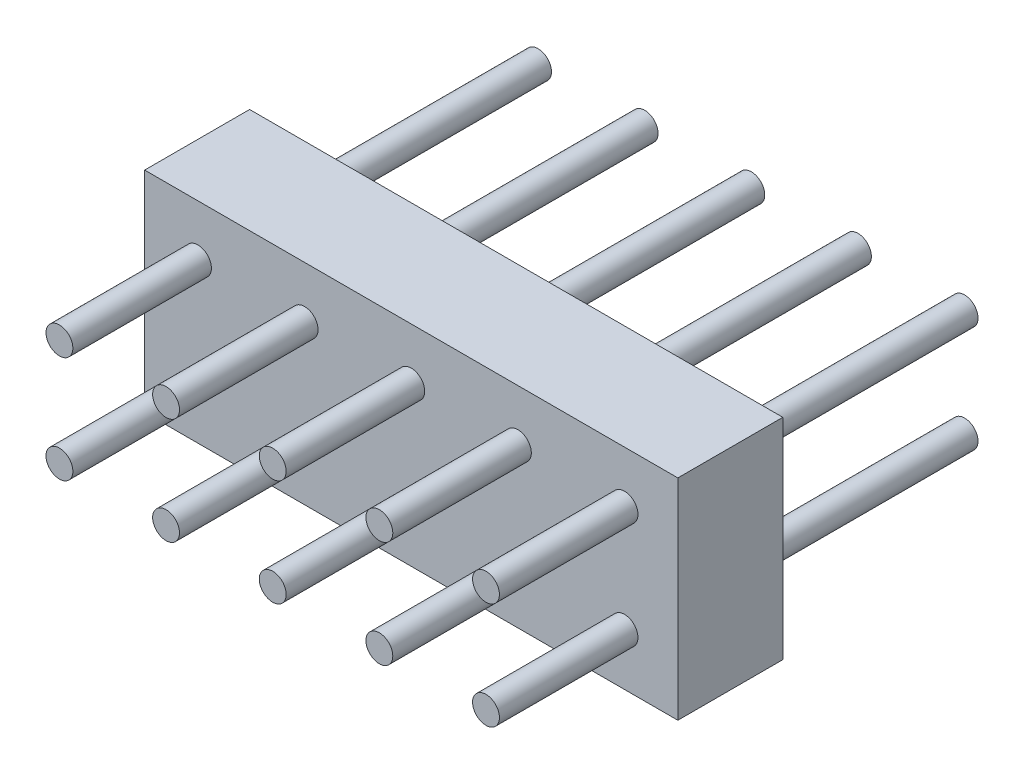
SolidWorks part; units mm, degrees
ref_plane "前视基准面" through (0, 0, 0) normal (0, 0, 1) x (1, 0, 0)
ref_plane "上视基准面" through (0, 0, 0) normal (0, 1, 0) x (1, 0, 0)
ref_plane "右视基准面" through (0, 0, 0) normal (1, 0, 0) x (0, 0, -1)
sketch "Sketch1" plane through (0, 0, 0) normal (0, 0, 1) x (1, 0, 0)
  line L1 (0, 0) -> (12.7, 0)
  line L2 (0, 0) -> (0, 5)
  line L3 (0, 5) -> (12.7, 5)
  line L4 (12.7, 0) -> (12.7, 5)
extrude "Boss-Extrude1" add sketch "Sketch1" along normal blind 2.5 contours L3 L4 L1 L2
sketch "Sketch2" plane through (0, 0, 2.5) normal (0, 0, 1) x (1, 0, 0)
  line L0 (0, 2.5) -> (14.858, 2.5) construction
  line L1 (0, 0) -> (0, 5) construction
  line L2 (6.35, 5) -> (6.35, -2.9072) construction
  line L3 (0, 5) -> (12.7, 5) construction
  circle A0 centre (1.27, 1.23) radius 0.32
  circle A1 centre (3.81, 1.23) radius 0.32
  circle A2 centre (6.35, 1.23) radius 0.32
  circle A3 centre (8.89, 1.23) radius 0.32
  circle A4 centre (11.43, 1.23) radius 0.32
  circle A5 centre (11.43, 3.77) radius 0.32
  circle A6 centre (8.89, 3.77) radius 0.32
  circle A7 centre (6.35, 3.77) radius 0.32
  circle A8 centre (3.81, 3.77) radius 0.32
  circle A9 centre (1.27, 3.77) radius 0.32
  dimension "D1" = 1.27
  dimension "D3" = 0.64
  dimension "D2" = 5.08
  dimension "D4" = 5
extrude "Boss-Extrude2" add sketch "Sketch2" along normal blind 3.3 contours A5 | A2 | A1 | A0 | A4 | A3 | A6 | A7 | A8 | A9
extrude "Boss-Extrude3" add sketch "Sketch2<4>" against normal blind 5.6 from surface starting at face at (6.35, 2.5, 0)
sketch "Sketch2<4>" plane through (0, 0, 2.5) normal (0, 0, 1) x (1, 0, 0) same geometry as "Sketch2"
